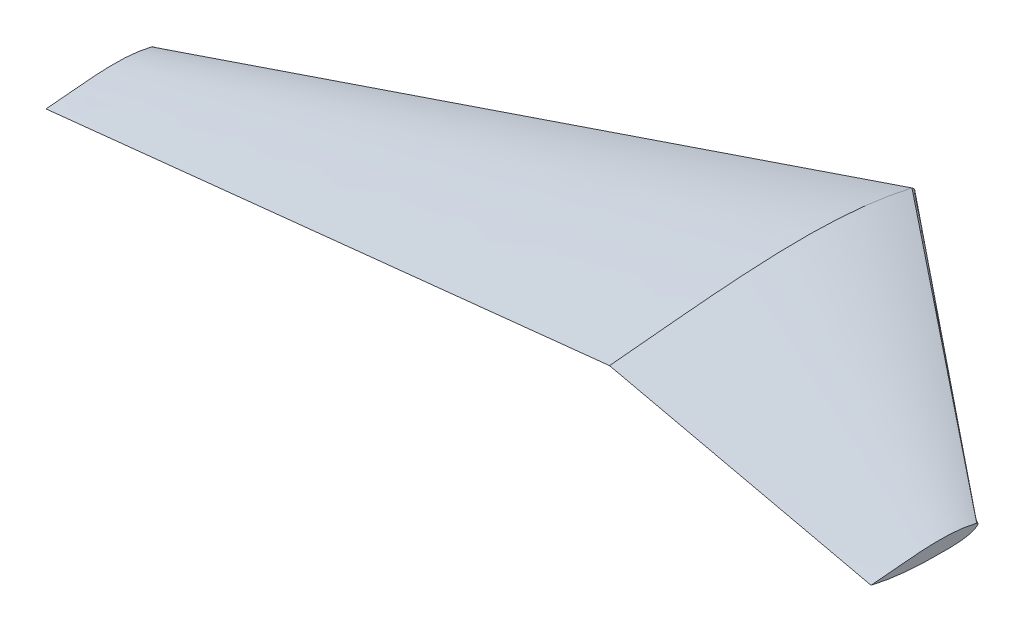
SolidWorks part; units mm, degrees
ref_plane "Front Plane" through (0, 0, 0) normal (0, 0, 1) x (1, 0, 0)
ref_plane "Top Plane" through (0, 0, 0) normal (0, 1, 0) x (1, 0, 0)
ref_plane "Right Plane" through (0, 0, 0) normal (1, 0, 0) x (0, 0, -1)
sketch "Sketch2" plane through (0, 0, 0) normal (0, 1, 0) x (1, 0, 0)
  line L0 (0, -5194.446) -> (0, 1731.482)
  line L1 (0, 0) -> (-18096.1342, 0) construction
  line L2 (0, 0) -> (-22098, -13277.818) construction
  line L3 (-22098, -15095.8741) -> (-22098, -12671.7993)
  line L4 (-22098, -12671.7993) -> (0, 1731.482)
  line L5 (-22098, -15095.8741) -> (0, -5194.446)
  line L6 (-9275.7037, -4314.3398) -> (-9275.7037, -5573.4051) construction
  line L7 (-9275.7037, -5573.4051) -> (-9275.7037, -9350.601) construction
  line L8 (-9275.7037, -5573.4051) -> (0, -5573.4051) construction
  line L9 (0, 346.2964) -> (-6827.52, -3825.6374)
  line L10 (0, -29565.6) -> (-5715.9144, -33718.4549) construction
  line L11 (0, -29565.6) -> (-8167.6786, -29565.6) construction
  line L12 (0, -28507.0982) -> (0, -32741.1055)
  line L13 (-5715.9144, -34829.8816) -> (-5715.9144, -33347.9793)
  line L14 (-5715.9144, -33347.9793) -> (0, -28507.0982)
  line L15 (0, -32741.1055) -> (-5715.9144, -34829.8816)
  line L16 (-2399.2704, -30539.071) -> (-2399.2704, -31308.772) construction
  line L17 (-2399.2704, -31308.772) -> (-2399.2704, -33617.8748) construction
  line L18 (-2399.2704, -31308.772) -> (0, -31308.772) construction
  line L19 (-6827.52, -3825.6374) -> (-6827.52, -6593.1427)
  line L20 (-6827.52, -6593.1427) -> (0, -3116.6676)
  line L21 (0, 346.2964) -> (0, -3116.6676) construction
  line L22 (0, -3116.6676) -> (0, 346.2964) construction
  line L23 (0, 346.2964) -> (0, -1385.1856) construction
  line L24 (0, 346.2964) -> (0, -3116.6676) construction
  line L25 (0, -1385.1856) -> (-6827.52, -5209.39) construction
  line L26 (0, 346.2964) -> (-22098, -13156.6142) construction
  line L27 (-3160.776, -1585.0854) -> (-3160.776, -3155.5874) construction
  line L28 (-3160.776, -3155.5874) -> (-3160.776, -4726.0893) construction
  line L29 (-3160.776, -3155.5874) -> (0, -3155.5874) construction
  line L30 (-5715.9144, -34229.7112) -> (0, -31026.3325) construction
  dimension "Wing Sweep" = 31
  dimension "Half Span" = 22098
  dimension "Wing Root" = 6925.928
  dimension "D4" = 1731.482
  dimension "Wing Tip" = 2424.0748
  dimension "D6" = 606.0187
  dimension "Wing YBar" = 9275.7037
  dimension "Tail Sweep" = 36
  dimension "Tail Root" = 4234.0073
  dimension "D10" = 1058.5018
  dimension "Tail Tip" = 1481.9022
  dimension "D12" = 370.4756
  dimension "D13" = 5715.9144
  dimension "Tail Ybar" = 2399.2704
  dimension "First Spar" = 1385.1856
  dimension "Second Spar" = 4848.1496
  dimension "Fuel Tip" = 2767.5053
  dimension "Tip Spar" = 484.815
  dimension "Fuel Ybar" = 3160.776
  dimension "Fuel Tank Length" = 6827.52
  dimension "Tail Arm" = 29565.6
  dimension "D2" = 2519.2343
  dimension "D3" = 881.7318
sketch "Sketch4" plane through (0, 0, 0) normal (0, 1, 0) x (1, 0, 0)
  line L0 (0, 18200.9949) -> (0, -34834.2051) construction
  line L1 (-2240.28, 18200.9949) -> (2240.28, 18200.9949) construction
  line L2 (-2240.28, 11480.1549) -> (-2240.28, -25873.0851)
  line L3 (-2240.28, -34834.2051) -> (2240.28, -34834.2051) construction
  line L4 (2240.28, 11480.1549) -> (2240.28, -25873.0851)
  line L5 (0, -5194.446) -> (0, 1731.482) construction
  line L6 (-9275.7037, -5573.4051) -> (0, -5573.4051) construction
  line L7 (-2399.2704, -31308.772) -> (0, -31308.772) construction
  line L8 (0, 0) -> (-22098, -13277.818) construction
  line L9 (-22098, -12671.7993) -> (0, 1731.482) construction
  line L10 (-8451.85, 1616.4392) -> (-6132.83, 1616.4392)
  line L11 (-8451.85, 1616.4392) -> (-8451.85, -3941.0808)
  line L12 (-8451.85, -3941.0808) -> (-6132.83, -3941.0808)
  line L13 (-6132.83, 1616.4392) -> (-6132.83, -3941.0808)
  line L14 (2240.28, 11480.1549) -> (-2240.28, 11480.1549)
  arc A0 (-2240.28, -25873.0851) -> (2240.28, -25873.0851) centre (0, -25873.0851) ccw construction
  spline S0 degree 2 poles (-2240.28, 11480.1549) (-2010.8321, 15064.3252) (0, 18200.9949) knots 0 0 0 1 1 1 construction
  spline S1 degree 2 poles (2240.28, 11480.1549) (2010.8321, 15064.3252) (0, 18200.9949) knots 0 0 0 1 1 1 construction
  spline S2 degree 3 poles (-2240.28, -25873.0851) (-2042.135, -27711.7659) (-2075.1921, -30173.7144) (-919.8513, -32825.3563) (0, -32741.1055) knots 0 0 0 0 0.711043 1 1 1 1 construction
  spline S3 degree 3 poles (2240.28, -25873.0851) (2042.135, -27711.7659) (2075.1921, -30173.7144) (919.8513, -32825.3563) (0, -32741.1055) knots 0 0 0 0 0.711043 1 1 1 1 construction
  spline S4 degree 2 poles (-2240.28, -25873.0851) (-2027.1744, -27637.7456) (0, -27753.3552) knots 0 0 0 1 1 1
  spline S5 degree 2 poles (2240.28, -25873.0851) (2027.1744, -27637.7456) (0, -27753.3552) knots 0 0 0 1 1 1
  point P6 (0, 11480.1549)
  point P7 (0, -25873.0851)
  point P8 (0, -5573.4051)
  point P15 (0, -28113.3651)
  point P28 (-7292.34, 1616.4392)
  point P29 (-7292.34, -3021.6008)
  point P35 (-7292.34, -4381.6799)
  point P44 (-7292.34, -606.5688)
  dimension "Fuse Length" = 53035.2
  dimension "Fuse Dia" = 4480.56
  dimension "D3" = 6720.84
  dimension "D4" = 8961.12
  dimension "D6" = 7292.34
  dimension "Engine Dia" = 2319.02
  dimension "Engine Length" = 5557.52
  dimension "D9" = 4638.04
  dimension "D10" = 2223.008
  dimension "D11" = 4966.8362
  dimension "D2" = 23774.4
ref_plane "Plane1" through (0, 609.6, 0) normal (0, 1, 0) x (1, 0, 0)
sketch "Sketch10" plane through (0, 0, 0) normal (0, 1, 0) x (1, 0, 0)
  line L0 (-22098, -12671.7993) -> (-2240.28, 271.2873)
  line L1 (-2240.28, 11480.1549) -> (-2240.28, -25873.0851) construction
  line L2 (-22098, -12671.7993) -> (-22098, -15095.8741)
  line L3 (-22098, -15095.8741) -> (-7292.34, -8461.9172)
  line L4 (-7292.34, -8461.9172) -> (-2240.28, -8461.9172)
  line L5 (-22098, -15095.8741) -> (0, -5194.446) construction
  line L6 (-22098, -12671.7993) -> (0, 1731.482) construction
  line L7 (-2240.28, -8461.9172) -> (-2240.28, 271.2873) construction
  line L9 (0, 271.2873) -> (0, -8461.9172)
  line L10 (0, -8461.9172) -> (-2240.28, -8461.9172)
  line L11 (0, -5194.446) -> (0, 1731.482) construction
  line L12 (-2240.28, 271.2873) -> (0, 1731.482)
  line L13 (0, 1731.482) -> (0, 271.2873)
ref_plane "Plane4" through (14059.0291, 0, 16600.3263) normal (0.6463, 0, 0.7631) x (0.7631, 0, -0.6463)
ref_plane "Plane2" through (-5715.9144, 0, 0) normal (1, 0, 0) x (0, 0, -1)
sketch "Sketch11" plane through (0, 0, 0) normal (1, 0, 0) x (0, 0, -1)
  line L0 (-31394.1382, -352.4096) -> (-30857.4716, -352.4096) construction
  line L1 (-28507.0982, 0) -> (-32741.1055, 0) construction
  spline S0 degree 3 poles (-32741.1055, 0) (-32087.6108, 58.4964) (-30694.3744, 215.6293) (-29283.3414, 206.7354) (-28550.6224, 37.3552) knots 0 0 0 0 0.467766 1 1 1 1
  spline S1 degree 3 poles (-32741.1055, 0) (-31699.0664, -259.8493) (-30612.0325, -286.5067) (-29544.5629, -281.2625) knots 0 0 0 0 1 1 1 1
  spline S2 degree 3 poles (-29544.5629, -281.2625) (-29299.6404, -272.429) (-28941.2534, -250.6732) (-28603.1064, -121.0879) (-28470.9045, -13.0597) (-28550.6224, 37.3552) knots 0 0 0 0 0.658433 0.851821 1 1 1 1
sketch "Sketch12" plane through (14059.0291, 0, 16600.3263) normal (0.6463, 0, 0.7631) x (0.7631, 0, -0.6463)
  line L0 (-18081.2415, -230.124) -> (-25913.9397, 1172.0272)
  line L1 (-18081.2415, 230.124) -> (-25926.1341, 1332.6518)
  line L2 (-18081.2415, 230.124) -> (-18081.2415, -230.124) construction
  line L3 (-25926.1341, 1332.6518) -> (-25913.9397, 1172.0272) construction
  line L4 (-18423.5587, 0) -> (-21159.9116, 0) construction
  line L6 (-25926.1341, 1332.6518) -> (-22696.9304, 1332.6518) construction
  point P1 (-18081.2415, 0)
  point P4 (-25926.1341, 1172.0272)
  dimension "D1" = 8
  dimension "D2" = 460.248
  dimension "D3" = 161.0868
sketch "Sketch13" plane through (-5715.9144, 0, 0) normal (1, 0, 0) x (0, 0, -1)
  line L0 (-34331.3091, -72.3608) -> (-33794.6424, -72.3608) construction
  spline S0 degree 2 poles (-33351.549, 1268.8208) (-33357.5305, 1279.8647) (-33369.9056, 1281.8781) knots 0 0 0 1 1 1
  spline S1 degree 3 poles (-33351.549, 1268.8208) (-33355.1901, 1255.6778) (-33376.7324, 1235.9443) (-33430.3621, 1208.7833) (-33514.0823, 1188.1973) (-33647.1422, 1172.6706) (-33814.8086, 1168.9804) (-34220.5191, 1175.6852) (-34563.7097, 1202.5227) (-34833.4512, 1268.8208) knots 0 0 0 0 0.026229 0.055394 0.119138 0.195327 0.321011 0.45098 1 1 1 1
  spline S2 degree 3 poles (-34833.4512, 1268.8208) (-34808.7282, 1273.8419) (-34743.6859, 1278.5458) (-34608.3542, 1291.0296) (-34406.6711, 1306.4675) (-33983.9683, 1346.9464) (-33628.1827, 1345.8385) (-33369.9056, 1281.8781) knots 0 0 0 0 0.051367 0.133023 0.277496 0.464226 1 1 1 1
loft "Loft1" add profiles "Sketch13", "Sketch11" connector at (-5715.9144, 1268.8208, 34833.4512) connector at (0, 0, 32741.1055)
mirror "Mirror1" about plane through (0, 0, 0) normal (1, 0, 0) of bodies 130
equation "\"D6@Sketch2\" = \"Wing Tip@Sketch2\" / 4"
equation "\"D4@Sketch2\" = \"Wing Root@Sketch2\" / 4"
equation "\"D10@Sketch2\" = \"Tail Root@Sketch2\" / 4"
equation "\"D12@Sketch2\" = \"Tail Tip@Sketch2\" / 4"
equation "\"D13@Sketch2\"=37.506/2"
equation "\"First Spar@Sketch2\"=0.2 * \"Wing Root@Sketch2\""
equation "\"Second Spar@Sketch2\"   = 0.7 * \"Wing Root@Sketch2\""
equation "\"Tip Spar@Sketch2\"=0.2 * \"Wing Tip@Sketch2\""
equation "\"D3@Sketch4\" = 1.5 * \"Fuse Dia@Sketch4\""
equation "\"D4@Sketch4\" = 2 * \"Fuse Dia@Sketch4\""
equation "\"D6@Sketch4\" = 0.33 * \"Half Span@Sketch2\""
equation "\"D9@Sketch4\" = 2 * \"Engine Dia@Sketch4\""
equation "\"D10@Sketch4\" = 0.40 * \"Engine Length@Sketch4\""
equation "\"D3@Sketch12\"=0.35*\"D2@Sketch12\""
equation "\"D2@Sketch2\"=0.595*\"Tail Root@Sketch2\""
equation "\"D3@Sketch2\"=.595*\"Tail Tip@Sketch2\""
